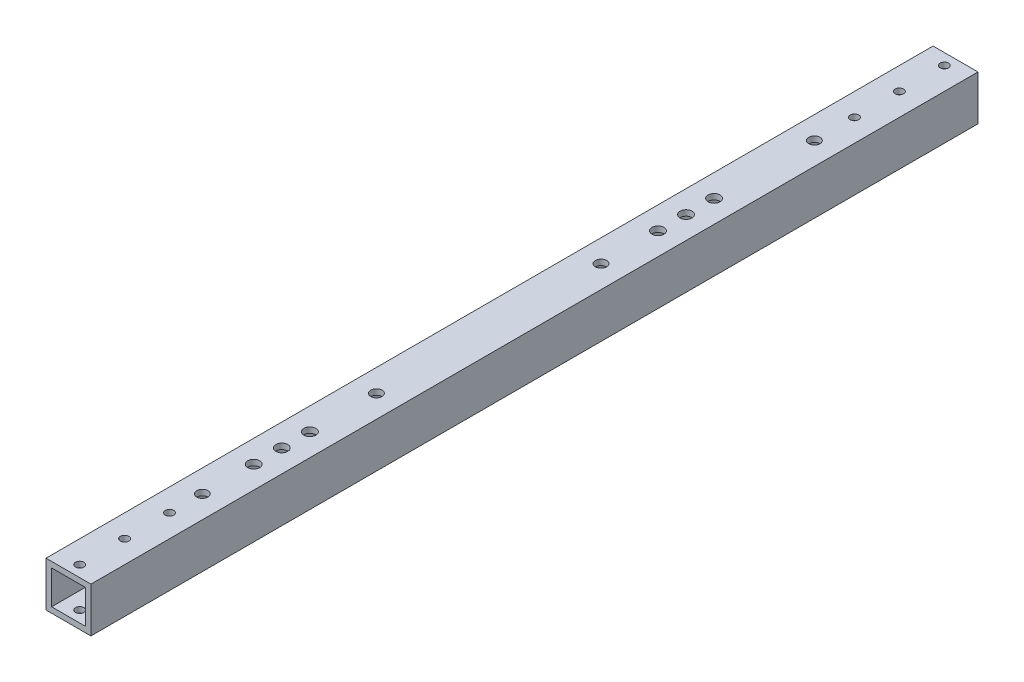
SolidWorks part; units mm, degrees
material "6061-T6 (SS)"
ref_plane "Front Plane" through (0, 0, 0) normal (0, 0, 1) x (1, 0, 0)
ref_plane "Top Plane" through (0, 0, 0) normal (0, 1, 0) x (1, 0, 0)
ref_plane "Right Plane" through (0, 0, 0) normal (1, 0, 0) x (0, 0, -1)
sketch "Sketch1" plane through (0, 0, 0) normal (0, 0, 1) x (1, 0, 0)
  line L1 (-12.7, -12.7) -> (12.7, -12.7)
  line L2 (-12.7, -12.7) -> (-12.7, 12.7)
  line L3 (-12.7, 12.7) -> (12.7, 12.7)
  line L4 (12.7, -12.7) -> (12.7, 12.7)
  line L5 (-12.7, -12.7) -> (12.7, 12.7) construction
  line L6 (-12.7, 12.7) -> (12.7, -12.7) construction
  point P0 (0, 0)
  dimension "D1" = 25.4
  dimension "D2" = 25.4
extrude "Extrude-Thin1" add sketch "Sketch1" along normal blind 501.65 thin thin type one direction reverse wall 3.175
hole_wizard "3/16 (0.1875) Diameter Hole1" positions "3DSketch1" profile "Sketch3" hole size "3/16" standard "ANSI Inch" end condition through all
sketch3d "3DSketch1"
  line L1 (12.7, 12.7, 0) -> (-12.7, 12.7, 0) construction
  line L6 (0, 12.7, 501.65) -> (0, 12.7, 0) construction
  line L7 (12.7, 12.7, 501.65) -> (-12.7, 12.7, 501.65) construction
  point P57 (0, 12.7, 6.35)
  point P59 (0, 12.7, 31.75)
  point P61 (0, 12.7, 57.15)
  point P63 (0, 12.7, 469.9)
  point P65 (0, 12.7, 444.5)
  point P67 (0, 12.7, 495.3)
  dimension "D1" = 25.4
  dimension "D2" = 25.4
  dimension "D3" = 6.35
  dimension "D4" = 25.4
  dimension "D5" = 25.4
  dimension "D6" = 6.35
sketch "Sketch3" plane through (0, 12.7, 495.3) normal (1, 0, 0) x (0, 0, 1)
  line L0 (0, 0) -> (0, 25.4)
  line L1 (0, 25.4) -> (2.3812, 25.4)
  line L2 (2.3812, 25.4) -> (2.3812, 0)
  line L5 (2.3812, 0) -> (0, 0)
  line L11 (0, -6.35) -> (0, 107.95) construction
  dimension "Thru Hole Dia." = 4.7625
  dimension "Thru Hole Depth" = 25.4
hole_wizard "1/4 (0.25) Diameter Hole1" positions "Sketch7" profile "Sketch6" hole size "1/4" standard "ANSI Inch"
sketch "Sketch7" plane through (0, 12.7, 0) normal (0, 1, 0) x (1, 0, 0)
  point P6 (0, -79.831)
  point P9 (0, -425.9339)
  point P23 (0, -327.499)
  point P26 (0, -200.481)
sketch "Sketch6" plane through (0, 12.7, 79.831) normal (1, 0, 0) x (0, 0, 1)
  line L0 (0, 0) -> (0, 27.3077)
  line L1 (0, 27.3077) -> (3.175, 25.4)
  line L2 (3.175, 25.4) -> (3.175, 0)
  line L5 (3.175, 0) -> (0, 0)
  line L10 (0, 27.3077) -> (-3.175, 25.4) construction
  line L11 (0, -6.35) -> (0, 107.95) construction
  dimension "Hole Dia." = 6.35
  dimension "Hole Depth" = 25.4
  dimension "Drill Angle" = 118
hole_wizard "1/4 Clearance Hole1" positions "Sketch8" profile "Sketch9" hole size "1/4" standard "ANSI Inch"
sketch "Sketch8" plane through (381, 25.4, 250.825) normal (0, 1, 0) x (1, 0, 0)
  point P0 (381, 82.55)
  point P3 (381, 98.425)
  point P6 (381, 114.3)
  point P9 (381, -146.05)
  point P12 (381, -130.175)
  point P15 (381, -114.3)
  point P18 (-381, -146.05)
  point P21 (-381, -130.175)
  point P24 (-381, -114.3)
  point P27 (-381, 82.55)
  point P30 (-381, 98.425)
  point P33 (-381, 114.3)
sketch "Sketch9" plane through (762, 25.4, 168.275) normal (1, 0, 0) x (0, 0, 1)
  line L0 (0, 0) -> (0, 40.1298)
  line L1 (0, 40.1298) -> (3.3782, 38.1)
  line L2 (3.3782, 38.1) -> (3.3782, 0)
  line L3 (3.3782, 0) -> (0, 0)
  line L4 (0, 40.1298) -> (-3.3782, 38.1) construction
  line L5 (0, -6.35) -> (0, 107.95) construction
  dimension "Hole Dia." = 6.7564
  dimension "Hole Depth" = 38.1
  dimension "Drill Angle" = 118
